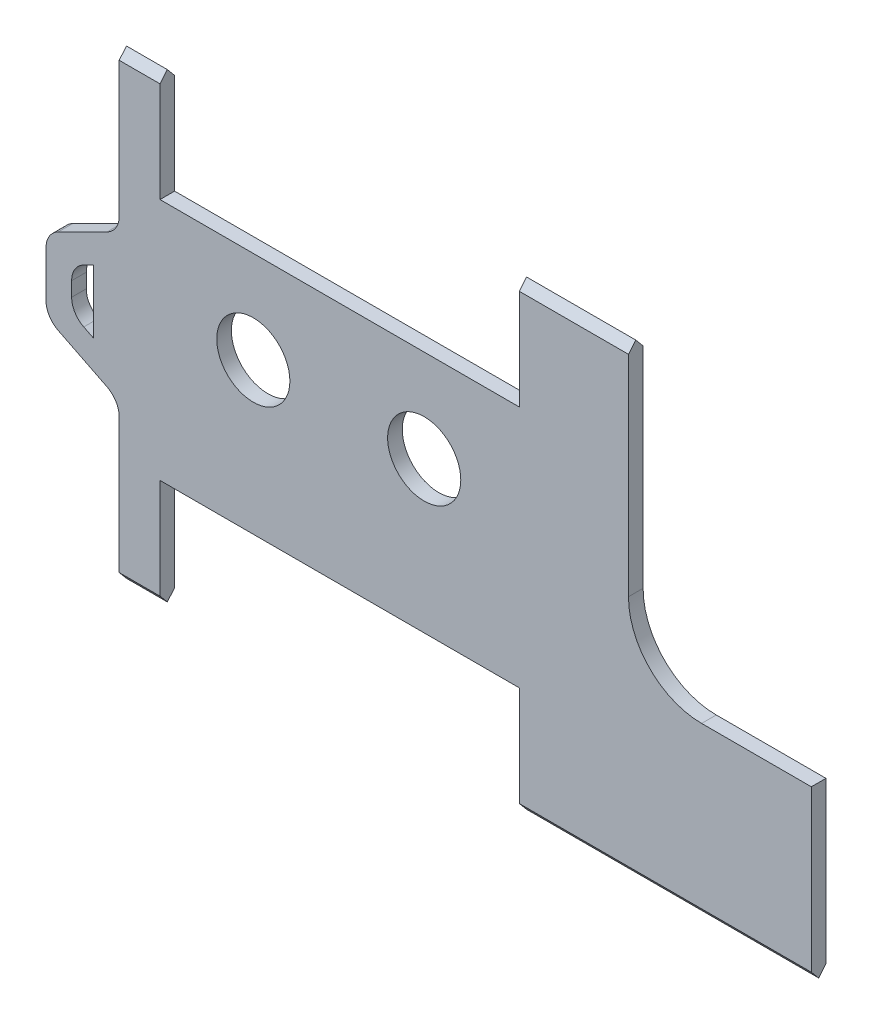
SolidWorks part; units mm, degrees
ref_plane "Front Plane" through (0, 0, 0) normal (0, 0, 1) x (1, 0, 0)
ref_plane "Top Plane" through (0, 0, 0) normal (0, 1, 0) x (1, 0, 0)
ref_plane "Right Plane" through (0, 0, 0) normal (1, 0, 0) x (0, 0, -1)
sketch "Sketch1" plane through (0, 0, 11.1483) normal (0, 0, 1) x (1, 0, 0)
  line L0 (22.423, 106.8975) -> (12.423, 101.8975)
  line L5 (22.223, 125.272) -> (22.223, 68.523) construction
  line L10 (12.423, 101.8975) -> (12.423, 91.8975)
  line L11 (117.248, 128.723) -> (22.223, 128.723) construction
  line L12 (117.248, 128.723) -> (117.248, 65.072) construction
  line L13 (117.248, 65.072) -> (22.223, 65.072) construction
  line L14 (22.223, 128.723) -> (22.223, 65.072) construction
  line L15 (117.048, 128.523) -> (22.423, 128.523)
  line L16 (22.423, 128.523) -> (22.423, 65.272)
  line L17 (117.048, 65.272) -> (22.423, 65.272)
  line L18 (117.048, 128.523) -> (117.048, 65.272)
  line L19 (12.423, 91.8975) -> (22.423, 86.8975)
  line L20 (92.048, 128.523) -> (92.048, 88.523)
  line L21 (92.048, 88.523) -> (117.048, 88.523)
  line L25 (22.423, 106.8975) -> (22.423, 86.8975)
  line L26 (15.923, 94.0606) -> (18.923, 92.5606)
  line L27 (18.923, 101.2344) -> (18.923, 92.5606)
  line L28 (18.923, 101.2344) -> (15.923, 99.7344)
  line L29 (15.923, 99.7344) -> (15.923, 94.0606)
  line L30 (-882.952, 96.8975) -> (49117.048, 96.8975) construction
  line L31 (28.005, 130.223) -> (28.005, 127.223) construction
  line L32 (28.005, 128.523) -> (77.123, 128.523)
  line L33 (28.005, 128.523) -> (28.005, 113.523)
  line L34 (28.005, 113.523) -> (77.123, 113.523)
  line L35 (77.123, 128.523) -> (77.123, 113.523)
  line L37 (77.123, 130.223) -> (77.123, 127.223) construction
  line L38 (28.005, 80.272) -> (77.123, 80.272)
  line L39 (77.123, 65.272) -> (77.123, 80.272)
  line L40 (28.005, 65.272) -> (77.123, 65.272)
  line L41 (28.005, 65.272) -> (28.005, 80.272)
  circle A0 centre (40.759, 100.906) radius 5
  circle A1 centre (64.123, 100.881) radius 5
  point P4 (22.423, 96.8975)
  point P8 (12.423, 96.8975)
  point P34 (117.048, 96.8975)
  point P40 (0, 0)
  point P48 (0, 0)
  point P49 (0, 0)
  point P51 (0, 0)
  dimension "D7" = 10
  dimension "D8" = 10
  dimension "D1" = 0.2
  dimension "D2" = 10
  dimension "D3" = 10
  dimension "D4" = 20
  dimension "D5" = 40
  dimension "D6" = 25
  dimension "D9" = 3.5
  dimension "D10" = 15
extrude "Boss-Extrude1" add sketch "Sketch1" along normal mid plane 2 contours L18 L15 L16 L17 | L10 L19 L16 L0 region at (22.1994, 96.8975, 11.1483) region at (67.7105, 93.2447, 11.1483)
sketch "Sketch2" plane through (22.423, 0, 0) normal (-1, 0, 0) x (0, 0, 1)
  line L5 (-986.1517, 96.8975) -> (49013.8483, 96.8975) construction
  line L6 (13.8483, 68.523) -> (13.8483, 125.272) construction
  line L7 (10.1013, 128.523) -> (10.1013, 127.1682)
  line L8 (12.1953, 127.1682) -> (11.1483, 128.4124)
  line L10 (12.1953, 66.6268) -> (12.1953, 65.272)
  line L11 (12.1953, 65.272) -> (10.1013, 65.272)
  line L12 (11.1483, 65.3826) -> (10.1013, 66.6268)
  line L13 (12.1953, 66.6268) -> (11.1483, 65.3826)
  line L14 (11.1483, 65.3826) -> (10.1013, 66.6268)
  line L15 (12.1953, 66.6268) -> (11.1483, 65.3826)
  line L16 (10.1013, 65.272) -> (10.1013, 66.6268)
  line L17 (12.1483, 65.272) -> (10.1483, 65.272) construction
  line L18 (11.1483, 128.4124) -> (10.1013, 127.1682)
  line L19 (12.1953, 128.523) -> (10.1013, 128.523)
  line L20 (12.1953, 127.1682) -> (12.1953, 128.523)
  point P9 (13.8483, 96.8975)
  dimension "D2" = 0.2
extrude "Cut-Extrude1" cut sketch "Sketch2" against normal through all
fillet "Fillet1" radius 10 1 edges at (92.048, 88.523, 11.1483)
fillet "Fillet2" radius 3 6 edges at (15.923, 99.7344, 11.1483) (15.923, 94.0606, 11.1483) (22.423, 106.8975, 11.1483) (12.423, 101.8975, 11.1483) (12.423, 91.8975, 11.1483) (22.423, 86.8975, 11.1483)
